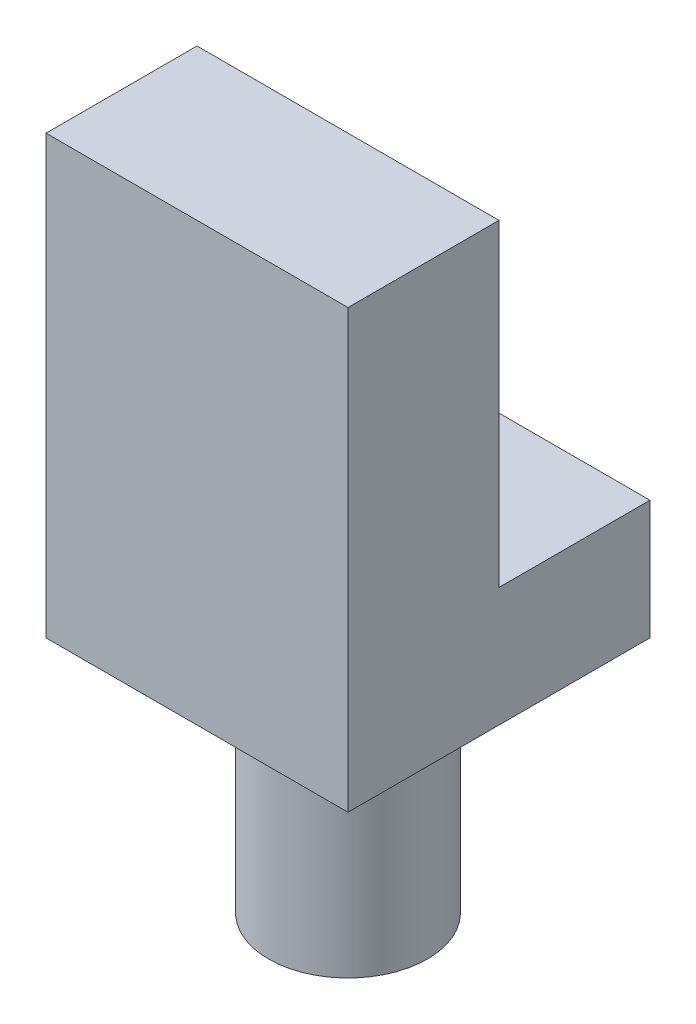
SolidWorks part; units mm, degrees
material "5086-H32, Rod (SS)"
ref_plane "Front Plane" through (0, 0, 0) normal (0, 0, 1) x (1, 0, 0)
ref_plane "Top Plane" through (0, 0, 0) normal (0, 1, 0) x (1, 0, 0)
ref_plane "Right Plane" through (0, 0, 0) normal (1, 0, 0) x (0, 0, -1)
sketch "Sketch1" plane through (0, 0, 0) normal (0, 1, 0) x (1, 0, 0)
  circle A0 centre (0, 0) radius 10
  dimension "D1" = 20
extrude "Boss-Extrude1" add sketch "Sketch1" along normal blind 30
sketch "Sketch2" plane through (0, 30, 0) normal (0, 1, 0) x (1, 0, 0)
  line L1 (-19, -19) -> (19, -19)
  line L2 (-19, -19) -> (-19, 19)
  line L3 (-19, 19) -> (19, 19)
  line L4 (19, -19) -> (19, 19)
  line L5 (-19, -19) -> (19, 19) construction
  line L6 (-19, 19) -> (19, -19) construction
  point P0 (0, 0)
  dimension "D1" = 38
extrude "Boss-Extrude2" add sketch "Sketch2" along normal blind 15
sketch "Sketch3" plane through (0, 45, 0) normal (0, 1, 0) x (1, 0, 0)
  line L0 (19, -19) -> (19, 19) construction
  line L1 (-19, -19) -> (19, -19)
  line L2 (-19, -19) -> (-19, 0)
  line L3 (-19, 0) -> (19, 0)
  line L4 (19, -19) -> (19, 0)
extrude "Boss-Extrude3" add sketch "Sketch3" along normal blind 40
sketch3d "3DSketch1"
  point P0 (19, 85, -29)
sketch3d "3DSketch2"
  point P0 (19, 85, -29)
